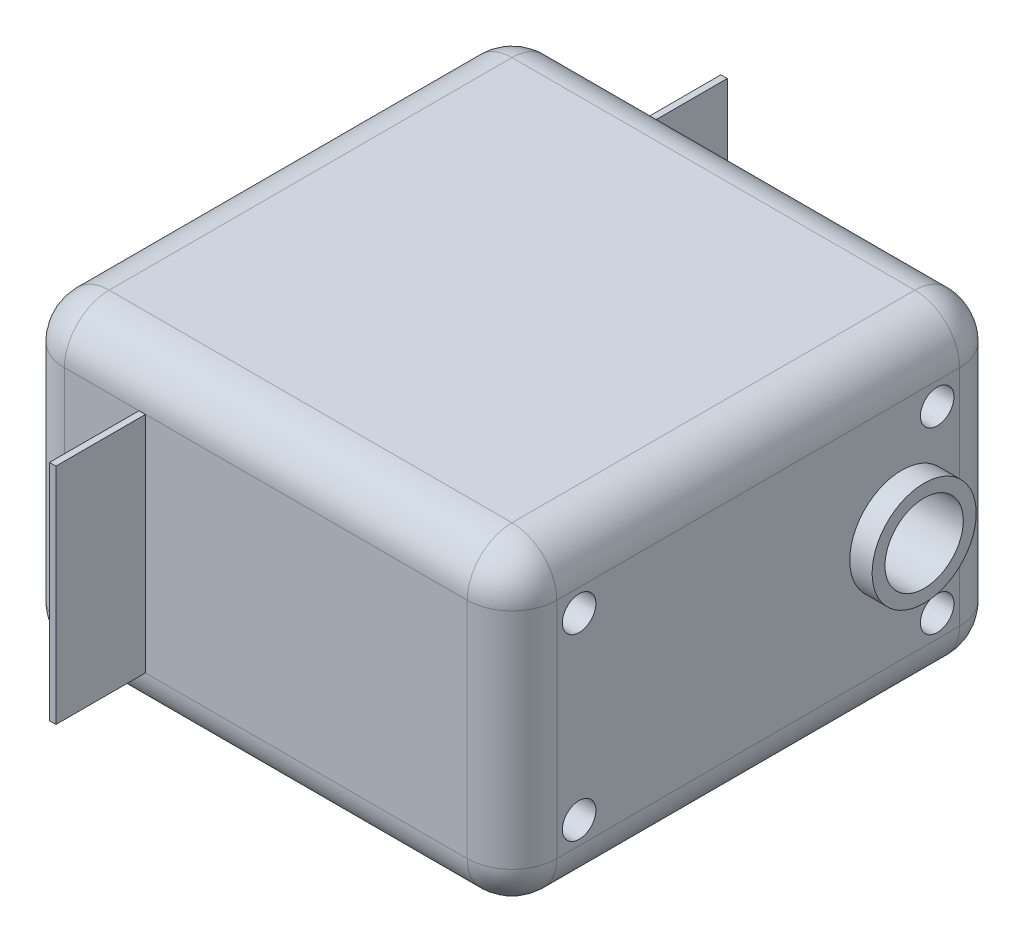
SolidWorks part; units mm, degrees
note: The reader was unsure of these and kept them because the rebuilt part matched: shared geometry of "Sketch5<2>".
ref_plane "Front Plane" through (0, 0, 0) normal (0, 0, 1) x (1, 0, 0)
ref_plane "Top Plane" through (0, 0, 0) normal (0, 1, 0) x (1, 0, 0)
ref_plane "Right Plane" through (0, 0, 0) normal (1, 0, 0) x (0, 0, -1)
sketch "Sketch1" plane through (0, 0, 0) normal (0, 0, 1) x (1, 0, 0)
  line L1 (-11, 7) -> (11, 7)
  line L2 (-11, 7) -> (-11, -7)
  line L3 (-11, -7) -> (11, -7)
  line L4 (11, 7) -> (11, -7)
  line L5 (-11, 7) -> (11, -7) construction
  line L6 (-11, -7) -> (11, 7) construction
  point P0 (0, 0)
  dimension "D1" = 14
  dimension "D2" = 22
extrude "Boss-Extrude1" add sketch "Sketch1" along normal mid plane 22
fillet "Fillet1" radius 2 12 edges at (0, -7, 11) (11, -7, 0) (11, 0, 11) (11, 7, 0) (0, 7, 11) (-11, 7, 0) (-11, 0, 11) (-11, -7, 0) (0, 7, -11) (-11, 0, -11) (0, -7, -11) (11, 0, -11)
sketch "Sketch4" plane through (11, 0, 0) normal (1, 0, 0) x (0, 0, -1)
  line L0 (9, -5) -> (9, 5) construction
  line L1 (-9, 5) -> (-9, -5) construction
  line L3 (-9, -5) -> (9, -5) construction
  line L4 (9, 5) -> (-9, 5) construction
  circle A0 centre (-8, 4) radius 0.75
  circle A1 centre (-8, -4) radius 0.75
  circle A2 centre (8, -4) radius 0.75
  circle A3 centre (8, 4) radius 0.75
  dimension "D1" = 1.5
  dimension "D2" = 1.5
  dimension "D3" = 1.5
  dimension "D4" = 1.5
  dimension "D5" = 1
  dimension "D6" = 1
  dimension "D7" = 1
  dimension "D8" = 1
extrude "Cut-Extrude1" cut sketch "Sketch4" against normal blind 28
sketch "Sketch5" plane through (11, 0, 0) normal (1, 0, 0) x (0, 0, -1)
  circle A0 centre (6.4164, 0) radius 2.3249
  circle A1 centre (6.4164, 0) radius 1.75
  dimension "D1" = 3.5
extrude "Boss-Extrude2" add sketch "Sketch5" along normal blind 1
extrude "Cut-Extrude2" cut sketch "Sketch5<2>" against normal blind 10 contours A1
sketch "Sketch5<2>" plane through (11, 0, 0) normal (1, 0, 0) x (0, 0, -1) same geometry as "Sketch5"
sketch "Sketch6" plane through (0, 0, -11) normal (0, 0, -1) x (-1, 0, 0)
  line L0 (9, 5) -> (-9, 5) construction
  line L1 (5.3802, 5) -> (5.667, 5)
  line L2 (5.3802, 5) -> (5.3802, -5)
  line L3 (5.3802, -5) -> (5.667, -5)
  line L4 (5.667, 5) -> (5.667, -5)
  line L5 (-9, -5) -> (9, -5) construction
extrude "Boss-Extrude3" add sketch "Sketch6" along normal blind 4 and the other way offset from surface (26 mm away) 4 other way up to face at (0, 0, 11)
